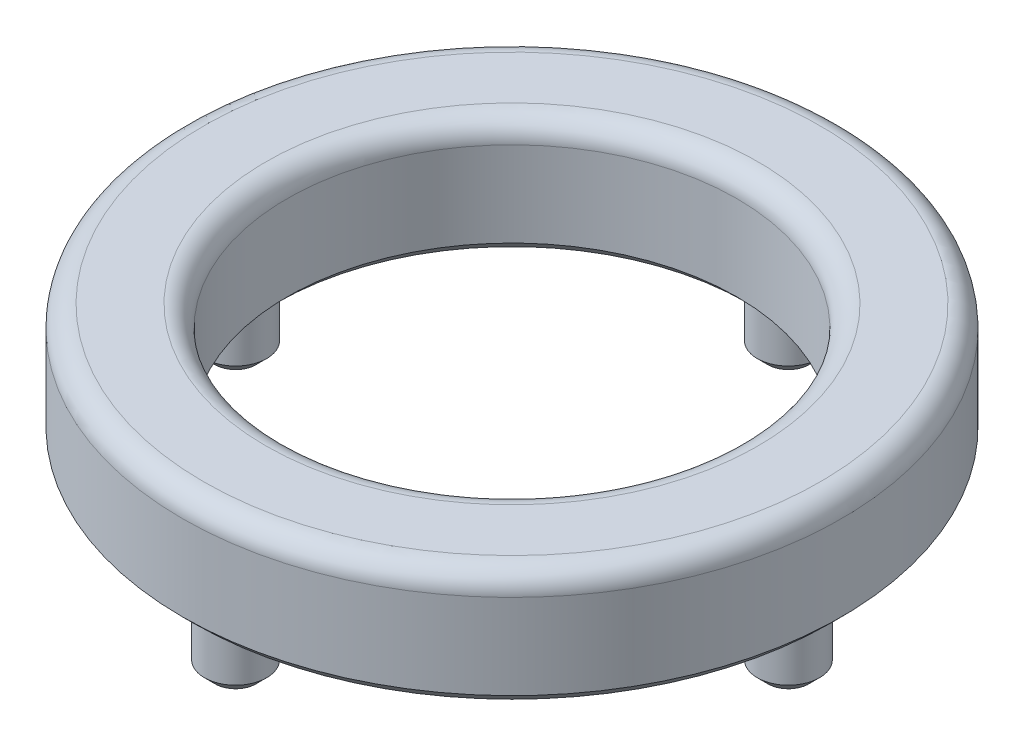
SolidWorks part; units mm, degrees
material "ABS"
ref_plane "Front" through (0, 0, 0) normal (0, 0, 1) x (1, 0, 0)
ref_plane "Top" through (0, 0, 0) normal (0, 1, 0) x (1, 0, 0)
ref_plane "Right" through (0, 0, 0) normal (1, 0, 0) x (0, 0, -1)
sketch "Эскиз1" plane through (0, 0, 0) normal (0, 1, 0) x (1, 0, 0)
  circle A0 centre (0, 0) radius 31
  circle A1 centre (0, 0) radius 21.15
  circle A2 centre (0, 0) radius 26 construction
  circle A3 centre (0, 26) radius 2.925
  circle A4 centre (26, 0) radius 2.925
  circle A5 centre (0, -26) radius 2.925
  circle A6 centre (-26, 0) radius 2.925
  dimension "D1" = 52
  dimension "D2" = 5.85
  dimension "D3" = 5.85
  dimension "D4" = 5.85
  dimension "D5" = 5.85
  dimension "D6" = 42.3
  dimension "D7" = 62
extrude "Бобышка-Вытянуть1" add sketch "Эскиз1" along normal blind 11 contours A1 | A0
extrude "Бобышка-Вытянуть2" add sketch "Эскиз1<3>" against normal blind 6 contours A3 | A5 | A6 | A4 region at (0, 0, -26)
sketch "Эскиз1<3>" plane through (0, 0, 0) normal (0, 1, 0) x (1, 0, 0) same geometry as "Эскиз1"
chamfer "Фаска1" distance 1 angle 45 4 edges at (-26, -6, 2.925) (0, -6, -23.075) (26, -6, 2.925) (0, -6, 28.925)
chamfer "Фаска2" distance 1 angle 45 2 edges at (0, 0, 21.15) (0, 0, 31)
fillet "Скругление1" radius 2 2 edges at (0, 11, 21.15) (0, 11, 31)
fillet "Скругление2" radius 0.4 4 edges at (26, 0, 2.925) (0, 0, 28.925) (-26, 0, 2.925) (0, 0, -23.075)
